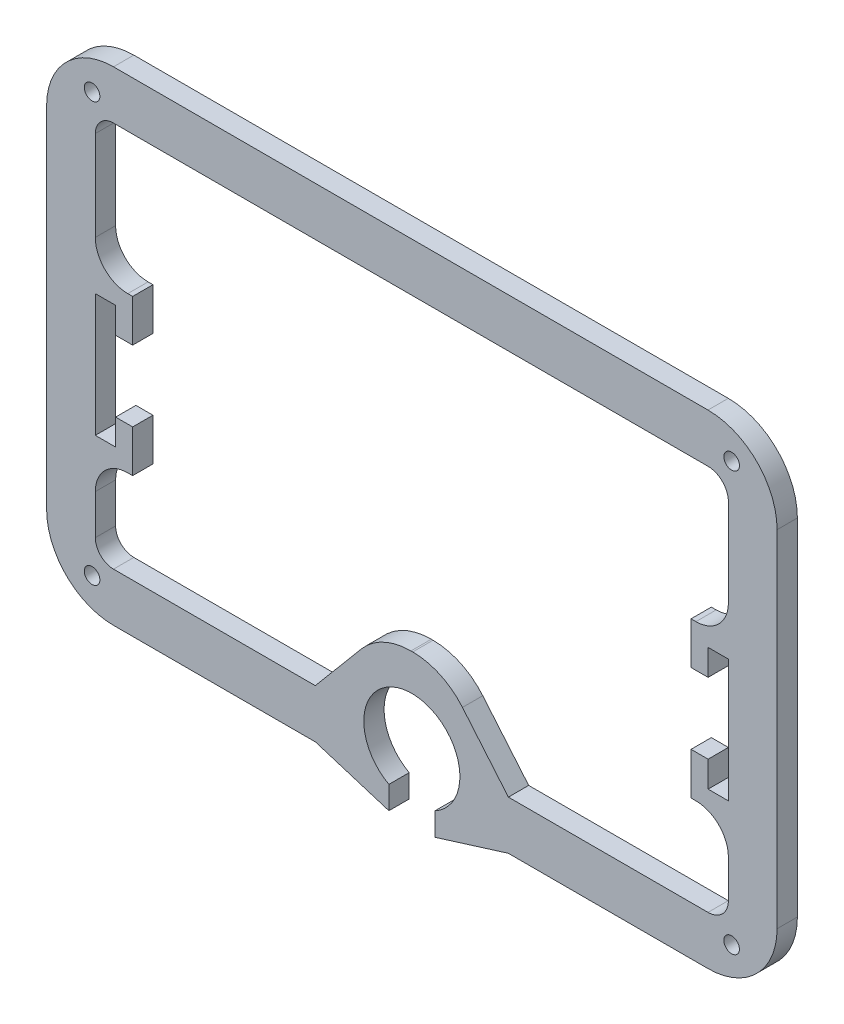
SolidWorks part; units mm, degrees
material "Delrin 2700 NC010, Low Viscosity Acetal Copolymer (SS)"
ref_plane "Front Plane" through (0, 0, 0) normal (0, 0, 1) x (1, 0, 0)
ref_plane "Top Plane" through (0, 0, 0) normal (0, 1, 0) x (1, 0, 0)
ref_plane "Right Plane" through (0, 0, 0) normal (1, 0, 0) x (0, 0, -1)
sketch "Sketch1" plane through (0, 0, 0) normal (0, 0, 1) x (1, 0, 0)
  line L0 (-23.3423, -18.923) -> (-7.5425, -18.923)
  line L1 (-24.765, 13.6903) -> (-24.765, -13.6903)
  line L2 (-23.3423, -15.113) -> (-7.5521, -15.113)
  line L3 (7.5521, -15.113) -> (23.1704, -15.113)
  line L4 (24.765, 13.5184) -> (24.765, -13.5184)
  line L5 (-1000, 0) -> (49000, 0) construction
  line L6 (-1.7968, -18.923) -> (-1.7968, -20.7107)
  line L7 (7.5425, -18.923) -> (23.1704, -18.923)
  line L8 (23.1704, 15.113) -> (-23.3423, 15.113)
  line L9 (-7.5521, -15.113) -> (-3.9596, -10.8316)
  line L10 (-28.575, 13.6903) -> (-28.575, -13.6903)
  line L11 (7.5521, -15.113) -> (3.9596, -10.8316)
  line L12 (-0.0681, -9.017) -> (0.0681, -9.017)
  line L13 (28.575, 13.5184) -> (28.575, -13.5184)
  line L14 (23.1704, 18.923) -> (-23.3423, 18.923)
  line L15 (1.7968, -18.923) -> (1.7968, -20.7107)
  line L16 (-7.5425, -18.923) -> (-1.7968, -20.7107)
  line L17 (7.5425, -18.923) -> (1.7968, -20.7107)
  line L18 (0, 12.5532) -> (0, -24.2768) construction
  line L19 (1.7968, -18.923) -> (23.1704, -18.923) construction
  line L20 (-23.3423, -18.923) -> (-1.7968, -18.923) construction
  line L21 (-24.765, 5.0849) -> (0, 5.0849) construction
  line L22 (0, 5.0849) -> (24.765, 5.0849) construction
  arc A0 (1.7968, -18.923) -> (-1.7968, -18.923) centre (0, -15.621) ccw
  arc A1 (-23.3423, -15.113) -> (-24.765, -13.6903) centre (-23.3423, -13.6903) cw
  arc A2 (-0.0681, -9.017) -> (-3.9596, -10.8316) centre (-0.0681, -14.097) ccw
  arc A3 (24.765, -13.5184) -> (23.1704, -15.113) centre (23.1704, -13.5184) cw
  arc A4 (23.1704, 15.113) -> (24.765, 13.5184) centre (23.1704, 13.5184) cw
  arc A5 (-23.3423, -18.923) -> (-28.575, -13.6903) centre (-23.3423, -13.6903) cw
  arc A6 (28.575, -13.5184) -> (23.1704, -18.923) centre (23.1704, -13.5184) cw
  arc A7 (23.1704, 18.923) -> (28.575, 13.5184) centre (23.1704, 13.5184) cw
  arc A8 (-23.3423, 18.923) -> (-28.575, 13.6903) centre (-23.3423, 13.6903) ccw
  circle A9 centre (-25.019, 16.383) radius 0.6096
  circle A10 centre (25.019, 16.383) radius 0.6096
  arc A11 (-23.3423, 15.113) -> (-24.765, 13.6903) centre (-23.3423, 13.6903) ccw
  arc A12 (0.0681, -9.017) -> (3.9596, -10.8316) centre (0.0681, -14.097) cw
  circle A13 centre (25.019, -16.383) radius 0.6096
  circle A14 centre (-25.019, -16.383) radius 0.6096
  circle A15 centre (0, -15.621) radius 5.3975 construction
  arc A18 (7.5521, -15.113) -> (-7.5521, -15.113) centre (0, -15.621) ccw construction
  point P0 (0, 0)
  dimension "D4" = 3.302
  dimension "D6" = 37.846
  dimension "D7" = 3.556
  dimension "D8" = 3.81
  dimension "D9" = 6.604
  dimension "D5" = 1.2192
  dimension "D2" = 49.53
  dimension "D3" = 7.5184
  dimension "D10" = 5.08
  dimension "D11" = 5.08
  dimension "D14" = 10.795
  dimension "D12" = 2.54
extrude "Boss-Extrude1" add sketch "Sketch1" along normal blind 1.5875
sketch "Sketch2" plane through (-24.765, 0, 0) normal (1, 0, 0) x (0, 0, -1)
  line L0 (0, 2.8448) -> (-1.5875, 2.8448)
  line L1 (0, -6.7596) -> (-1.5875, -6.7596) construction
  line L2 (-1.5875, -15.113) -> (0, -15.113)
  line L3 (-1.5875, -15.113) -> (0, -15.113) construction
  line L4 (0, -13.6903) -> (0, 13.6903)
  line L5 (0, 13.6903) -> (-1.5875, 13.6903)
  line L6 (-1.5875, 13.6903) -> (-1.5875, -13.6903)
  line L7 (0, 13.6903) -> (-1.5875, 13.6903)
  line L8 (0, -13.6903) -> (0, 4.1148)
  line L9 (-1.5875, -15.113) -> (-1.5875, -8.0296)
  line L10 (-1.5875, 4.1148) -> (-1.5875, -13.6903)
  line L11 (-1.5875, -13.6903) -> (0, -13.6903)
  line L12 (0, -15.113) -> (0, -8.0296)
  line L13 (0, 4.1148) -> (-1.5875, 4.1148)
  line L14 (-1.5875, 2.8448) -> (-1.5875, -6.6447)
  line L15 (-1.5875, 4.1148) -> (-1.5875, 2.8448)
  line L16 (0, 2.8448) -> (0, 4.1148)
  line L17 (0, -7.9147) -> (0, 1.4693)
  line L18 (-1.5875, -7.9147) -> (-1.5875, -6.6447)
  line L19 (0, -6.7596) -> (-1.5875, -6.7596)
  line L21 (0, -8.0296) -> (-1.5875, -8.0296)
  line L22 (0, -8.0296) -> (0, -13.6903)
  line L23 (-1.5875, -8.0296) -> (-1.5875, -13.6903)
  line L24 (47.9467, 2.8448) -> (1.4151, 2.8448) construction
  line L28 (-1.5875, -13.6903) -> (0, -13.6903)
  line L29 (47.5608, -9.6909) -> (1.4354, -6.848) construction
  line M5 (0, -13.6903) -> (0, 13.6903)
  line M7 (-1.5875, 13.6903) -> (-1.5875, -13.6903)
  dimension "D1" = 0
  dimension "D2" = 1.27
  dimension "D4" = 1.27
extrude "Boss-Extrude2" add sketch "Sketch2" along normal blind 2.921 contours L13 L10 L0 M5 | L19 L17 L8 L0 L10 M7 | L21 L8 L19 L18 M5 M7 region at (-24.765, -1.9574, 0.7937) region at (-24.765, 3.4798, 0.7937) region at (-24.765, -7.3946, 0.7937)
extrude "Cut-Extrude1" cut sketch "Sketch2<3>" along normal blind 1.5875 contours L19 L17 L0 M5 M7 region at (-24.765, -1.9574, 0.7937)
sketch "Sketch2<3>" plane through (-24.765, 0, 0) normal (1, 0, 0) x (0, 0, -1) same geometry as "Sketch2"
sketch "Sketch3" plane through (-23.1775, 0, 0) normal (-1, 0, 0) x (0, 0, 1)
  line L0 (0, 2.8448) -> (1.5875, 2.8448) construction
  line L1 (0, -6.7596) -> (1.5875, -6.7596) construction
  line L2 (0, 2.8448) -> (1.5875, 2.8448)
  line L3 (0, -6.7596) -> (1.5875, -6.7596)
  line L4 (0, 0.8128) -> (1.5875, 0.8128)
  line L5 (0, -4.7276) -> (1.5875, -4.7276)
  line L6 (1.5875, 0.8128) -> (1.5875, -4.7276)
  line L7 (0, -4.7276) -> (0, 0.8128)
  line M2 (1.5875, -6.7596) -> (1.5875, 2.8448)
  line M4 (0, 2.8448) -> (0, -6.7596)
  dimension "D1" = 2.032
  dimension "D2" = 2.032
extrude "Cut-Extrude2" cut sketch "Sketch3" against normal up to surface (1.3335 mm away) contours L5 L4 M4 M2 region at (-23.1775, -1.9574, 0.7937) up to face at (-21.844, -1.9574, 0.7937)
mirror "Mirror1" about plane through (0, 0, 0) normal (1, 0, 0) of "Cut-Extrude2", "Boss-Extrude2", "Cut-Extrude1"
fillet "Fillet5" radius 2.54 4 edges at (24.765, 4.1148, 0.7937) (24.765, -8.0296, 0.7937) (-24.765, -8.0296, 0.7937) (-24.765, 4.1148, 0.7937)
